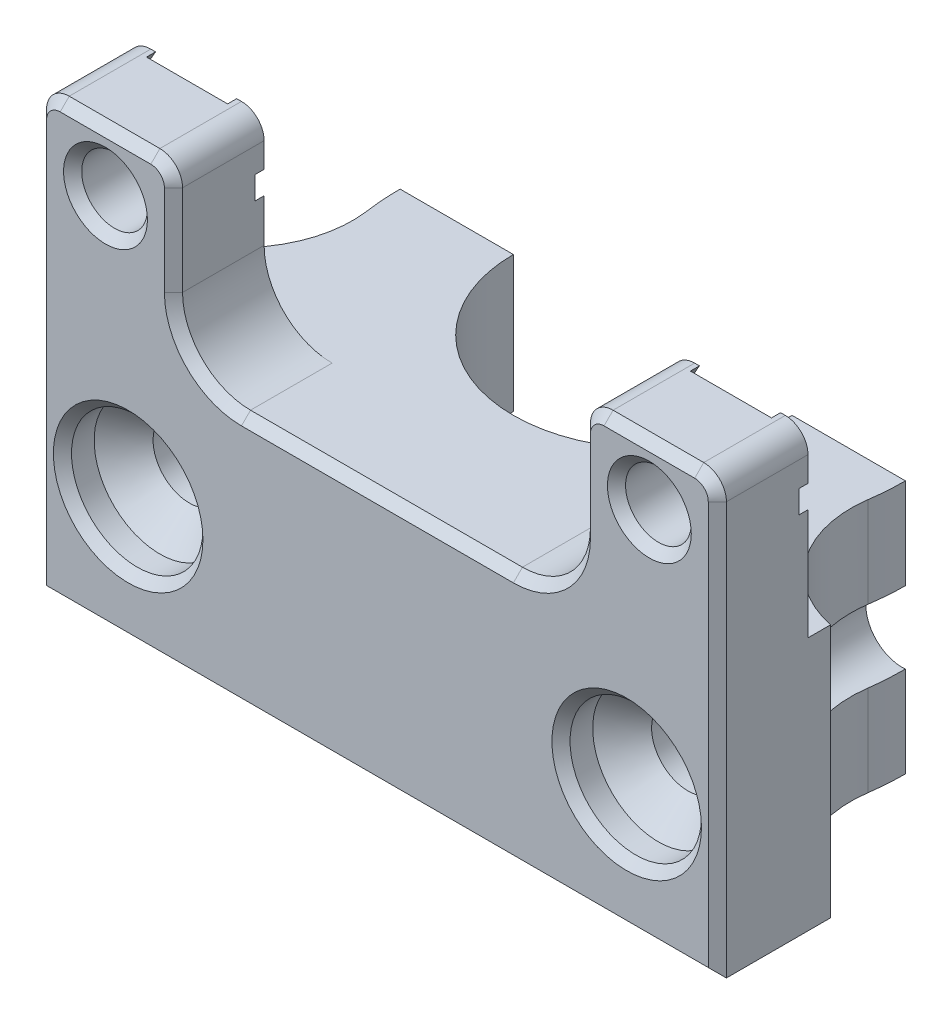
SolidWorks part; units mm, degrees
ref_plane "前视基准面" through (0, 0, 0) normal (0, 0, 1) x (1, 0, 0)
ref_plane "上视基准面" through (0, 0, 0) normal (0, 1, 0) x (1, 0, 0)
ref_plane "右视基准面" through (0, 0, 0) normal (1, 0, 0) x (0, 0, -1)
other "Configuration Table"
sketch "草图1" plane through (0, 0, 0) normal (0, 1, 0) x (1, 0, 0)
  line L0 (-11.15, 0) -> (-8.15, 0)
  line L1 (8.15, 0) -> (11.15, 0)
  arc A0 (-8.15, 0) -> (8.15, 0) centre (0, 0) ccw
  arc A1 (-11.15, 0) -> (11.15, 0) centre (0, 0) ccw
  circle A3 centre (0, 0) radius 11.15 construction
  circle A4 centre (0, 0) radius 8.15 construction
  point P4 (7.7939, 2.3828)
  point P7 (11.15, 0)
  dimension "D1" = 16.3
  dimension "D2" = 3
extrude "凸台-拉伸1" add sketch "草图1" along normal blind 5.2
sketch "草图2" plane through (0, 5.2, 0) normal (0, 1, 0) x (1, 0, 0)
  line L0 (-11.15, 0) -> (-6.15, 0)
  line L1 (6.15, 0) -> (11.15, 0)
  arc A0 (-11.15, 0) -> (11.15, 0) centre (0, 0) ccw
  arc A1 (-6.15, 0) -> (6.15, 0) centre (0, 0) ccw
  dimension "D1" = 12.3
extrude "凸台-拉伸2" add sketch "草图2" along normal blind 6
sketch "草图3" plane through (0, 11.2, 0) normal (0, 1, 0) x (1, 0, 0)
  line L0 (3.9115, -7.15) -> (15, -7.15)
  line L1 (-15, -7.15) -> (-3.9115, -7.15)
  line L2 (-15, -7.15) -> (-15, -11.15)
  line L3 (-15, -11.15) -> (15, -11.15)
  line L4 (15, -7.15) -> (15, -11.15)
  arc A0 (-11.15, 0) -> (11.15, 0) centre (0, 0) ccw construction
  arc A1 (-3.9115, -7.15) -> (3.9115, -7.15) centre (0, 0) ccw
  point P7 (0, -11.15)
  dimension "D1" = 11.15
  dimension "D2" = 30
  dimension "D3" = 0
  dimension "D4" = 4
extrude "凸台-拉伸3" add sketch "草图3" against normal up to surface (11.2 mm away) up to face at (0, 0, 4.825)
fillet "圆角1" radius 5 2 edges at (-8.5557, 5.6, 7.15) (8.5557, 5.6, 7.15)
sketch "草图4" plane through (0, 0, 11.15) normal (0, 0, 1) x (1, 0, 0)
  line L0 (-15, 0) -> (-15, 11.2) construction
  line L1 (15, 0) -> (15, 11.2) construction
  line L2 (-15, 11.2) -> (15, 11.2) construction
  circle A0 centre (-11, 5.6) radius 1.6
  circle A1 centre (11, 5.6) radius 1.6
  point P6 (-15, 5.6)
  point P9 (15, 5.6)
  point P12 (0, 11.2)
  dimension "D1" = 3.2
  dimension "D2" = 3.2
  dimension "D3" = 0
  dimension "D4" = 0
  dimension "D5" = 11
  dimension "D6" = 11
extrude "切除-拉伸1" cut sketch "草图4" against normal through all
sketch "草图7" plane through (0, 11.2, 0) normal (0, 1, 0) x (1, 0, 0)
  line L1 (-15, -11.15) -> (-9, -11.15)
  line L2 (-15, -11.15) -> (-15, -8.15)
  line L3 (-15, -8.15) -> (-9, -8.15)
  line L4 (-9, -11.15) -> (-9, -8.15)
  line L5 (15, -11.15) -> (9, -11.15)
  line L6 (15, -11.15) -> (15, -8.15)
  line L7 (15, -8.15) -> (9, -8.15)
  line L8 (9, -11.15) -> (9, -8.15)
  dimension "D1" = 3
  dimension "D2" = 3
  dimension "D3" = 6
  dimension "D4" = 6
extrude "凸台-拉伸5" add sketch "草图7" along normal blind 8
sketch "草图8" plane through (0, 0, 11.15) normal (0, 0, 1) x (1, 0, 0)
  line L0 (-15, 0) -> (-15, 19.2) construction
  circle A0 centre (-12, 16.6) radius 1.45
  circle A1 centre (12, 16.6) radius 1.45
  circle A2 centre (-11, 5.6) radius 1.6 construction
  circle A3 centre (11, 5.6) radius 1.6 construction
  dimension "D1" = 2.9
  dimension "D2" = 2.9
  dimension "D3" = 24
  dimension "D4" = 11
  dimension "D5" = 11
  dimension "D6" = 3
extrude "切除-拉伸3" cut sketch "草图8" against normal blind 8
sketch "草图9" plane through (0, 0, 11.15) normal (0, 0, 1) x (1, 0, 0)
  line L16 (-15, 19.2) -> (-15, 0)
  line L17 (-15, 0) -> (15, 0)
  line L18 (15, 0) -> (15, 19.2)
  line L19 (15, 19.2) -> (9, 19.2)
  line L20 (9, 19.2) -> (9, 11.2)
  line L21 (9, 11.2) -> (-9, 11.2)
  line L22 (-9, 11.2) -> (-9, 19.2)
  line L23 (-9, 19.2) -> (-15, 19.2)
  line L24 (-15, 19.2) -> (-15, 0)
  line L25 (-15, 0) -> (15, 0)
  line L26 (15, 0) -> (15, 19.2)
  line L27 (15, 19.2) -> (9, 19.2)
  line L28 (9, 19.2) -> (9, 11.2)
  line L29 (9, 11.2) -> (-9, 11.2)
  line L30 (-9, 11.2) -> (-9, 19.2)
  line L31 (-9, 19.2) -> (-15, 19.2)
  circle A0 centre (-12, 16.6) radius 1.45
  circle A1 centre (-11, 5.6) radius 1.6
  circle A2 centre (11, 5.6) radius 1.6
  circle A3 centre (12, 16.6) radius 1.45
  dimension "D1" = 0
extrude "凸台-拉伸6" add sketch "草图9" along normal blind 1
fillet "圆角2" radius 3 2 edges at (9, 11.2, 10.15) (-9, 11.2, 10.15)
fillet "圆角3" radius 1 4 edges at (15, 19.2, 10.15) (9, 19.2, 10.15) (-9, 19.2, 10.15) (-15, 19.2, 10.15)
sketch "草图10" plane through (0, 0, 12.15) normal (0, 0, 1) x (1, 0, 0)
  circle A0 centre (-11, 5.6) radius 2.9
  circle A1 centre (11, 5.6) radius 2.9
  dimension "D1" = 5.8
  dimension "D2" = 5.8
extrude "切除-拉伸4" cut sketch "草图10" against normal blind 2.7
chamfer "倒角2" distance 1.3 angle 45 2 edges at (-8.1, 5.6, 9.45) (13.9, 5.6, 9.45)
chamfer "倒角1" distance 0.4 angle 45 18 edges at (13.45, 16.6, 12.15) (0, 0, 12.15) (-15, 9.1, 12.15) (-14.7071, 18.9071, 12.15) (-12, 19.2, 12.15) (-9.2929, 18.9071, 12.15) (-9, 16.2, 12.15) (-8.1213, 12.0787, 12.15) (0, 11.2, 12.15) (8.1213, 12.0787, 12.15) (9, 16.2, 12.15) (9.2929, 18.9071, 12.15) (12, 19.2, 12.15) (14.7071, 18.9071, 12.15) (15, 9.1, 12.15) (-10.55, 16.6, 12.15) (13.9, 5.6, 12.15) (-8.1, 5.6, 12.15)
sketch "草图11" plane through (0, 0, 8.15) normal (0, 0, -1) x (-1, 0, 0)
  line L1 (-8.7091, 16.6) -> (-10.3546, 19.45)
  line L2 (-10.3546, 19.45) -> (-13.6454, 19.45)
  line L3 (-13.6454, 19.45) -> (-15.2909, 16.6)
  line L4 (-15.2909, 16.6) -> (-13.6454, 13.75)
  line L5 (-13.6454, 13.75) -> (-10.3546, 13.75)
  line L6 (-10.3546, 13.75) -> (-8.7091, 16.6)
  line L7 (15.2909, 16.6) -> (13.6454, 19.45)
  line L8 (13.6454, 19.45) -> (10.3546, 19.45)
  line L9 (10.3546, 19.45) -> (8.7091, 16.6)
  line L10 (8.7091, 16.6) -> (10.3546, 13.75)
  line L11 (10.3546, 13.75) -> (13.6454, 13.75)
  line L12 (13.6454, 13.75) -> (15.2909, 16.6)
  circle A0 centre (-12, 16.6) radius 2.85 construction
  circle A1 centre (12, 16.6) radius 2.85 construction
  dimension "D1" = 5.7
  dimension "D2" = 5.7
extrude "切除-拉伸5" cut sketch "草图11" against normal blind 0.4
equation "\"D1@草图3\"=22.3/2"
equation "\"D5@草图8\"=\"D4@草图8\""
